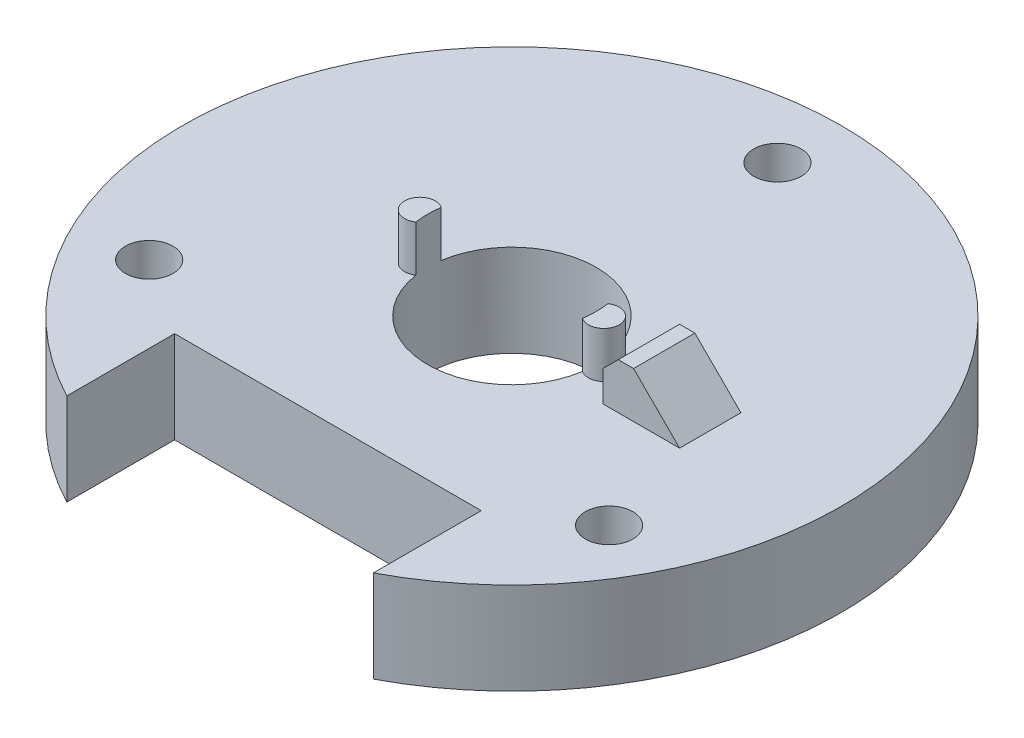
SolidWorks part; units mm, degrees
ref_plane "Front Plane" through (0, 0, 0) normal (0, 0, 1) x (1, 0, 0)
ref_plane "Top Plane" through (0, 0, 0) normal (0, 1, 0) x (1, 0, 0)
ref_plane "Right Plane" through (0, 0, 0) normal (1, 0, 0) x (0, 0, -1)
sketch "Sketch1" plane through (0, 0, 0) normal (0, 1, 0) x (1, 0, 0)
  circle A0 centre (0, 17.3208) radius 1.55
  circle A1 centre (15, -8.66) radius 1.55
  circle A2 centre (-15, -8.66) radius 1.55
  circle A4 centre (0, 0) radius 21.5
  dimension "D5" = 3.1
  dimension "D6" = 3.1
  dimension "D7" = 3.1
  dimension "D8" = 43
  dimension "D1" = 30
  dimension "D2" = 8.66
  dimension "D3" = 30
  dimension "D4" = 30
extrude "Boss-Extrude1" add sketch "Sketch1" along normal blind 6
sketch "Sketch2" plane through (0, 0, 0) normal (0, -1, 0) x (-1, 0, 0)
  line L1 (-10, -12) -> (10, -12)
  line L2 (-10, -12) -> (-10, -22)
  line L3 (-10, -22) -> (10, -22)
  line L4 (10, -12) -> (10, -22)
  circle A0 centre (0, 0) radius 5.5
  point P7 (0, -12)
  dimension "D1" = 11
  dimension "D2" = 20
  dimension "D3" = 12
  dimension "D4" = 10
extrude "Cut-Extrude1" cut sketch "Sketch2" against normal blind 12
sketch "Sketch3" plane through (0, 6, 0) normal (0, 1, 0) x (1, 0, 0)
  arc A0 (-5.4375, 0.8268) -> (-5.4375, -0.8268) centre (-6, 0) ccw
  arc A1 (5.4375, -0.8268) -> (5.4375, 0.8268) centre (6, 0) ccw
  circle A2 centre (0, 0) radius 5.5 construction
  arc A3 (-5.4375, 0.8268) -> (-5.4375, -0.8268) centre (0, 0) ccw
  arc A4 (5.4375, -0.8268) -> (5.4375, 0.8268) centre (0, 0) ccw
  point P7 (0, 0)
  dimension "D2" = 2
  dimension "D1" = 6
  dimension "D3" = 2
extrude "Boss-Extrude2" add sketch "Sketch3" along normal blind 3
sketch "Sketch4" plane through (0, 6, 0) normal (0, 1, 0) x (1, 0, 0)
  line L1 (7.9375, 2) -> (9.9375, 2)
  line L2 (7.9375, 2) -> (7.9375, -2)
  line L3 (7.9375, -2) -> (9.9375, -2)
  line L4 (9.9375, 2) -> (9.9375, -2)
  arc A0 (5.4375, -0.8268) -> (5.4375, 0.8268) centre (0, 0) ccw construction
  point P7 (5.5, 0)
  dimension "D1" = 2
  dimension "D2" = 4
  dimension "D3" = 2.5
  dimension "D4" = 2
extrude "Boss-Extrude3" add sketch "Sketch4" along normal blind 3
chamfer "Chamfer1" distance 1 angle 45 1 edges at (7.9375, 9, 0)
chamfer "Chamfer2" distance 3 angle 45 1 edges at (9.9375, 6, 0)
